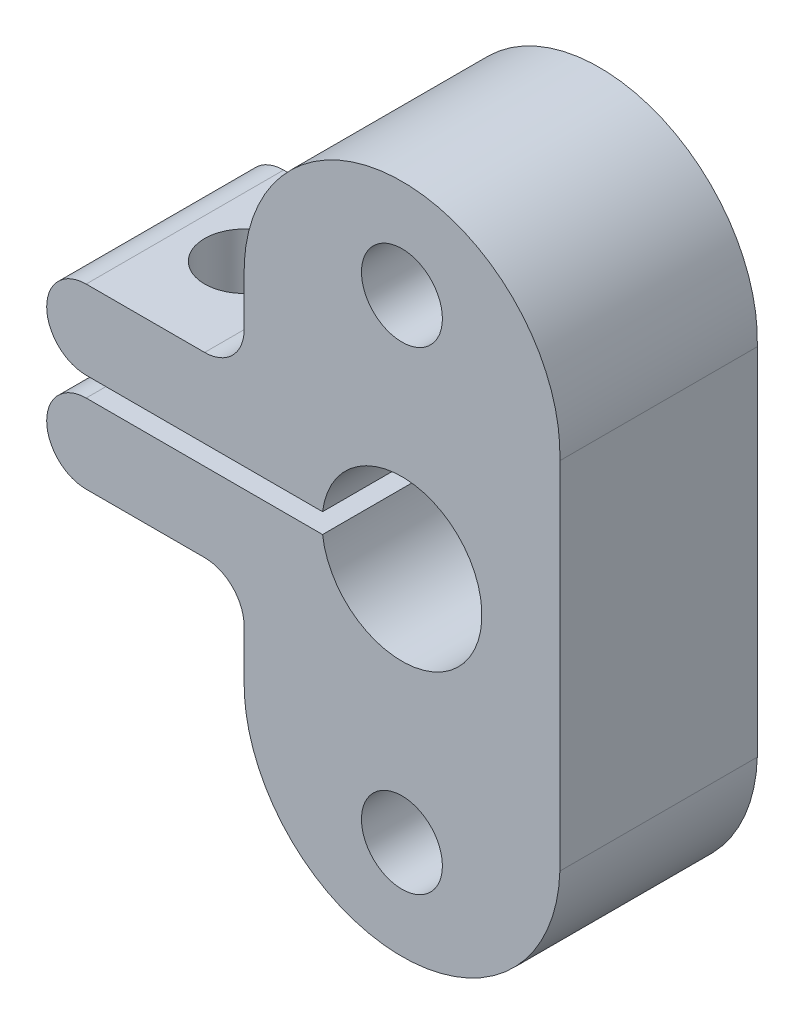
SolidWorks part; units mm, degrees
ref_plane "Plano frontal" through (0, 0, 0) normal (0, 0, 1) x (1, 0, 0)
ref_plane "Plano superior" through (0, 0, 0) normal (0, 1, 0) x (1, 0, 0)
ref_plane "Plano direito" through (0, 0, 0) normal (1, 0, 0) x (0, 0, -1)
sketch "Esboço1" plane through (0, 0, 0) normal (0, 0, 1) x (1, 0, 0)
  line L0 (0.004, -9.0015) -> (0.004, 9.0015) construction
  line L1 (-7.992, -8.75) -> (-7.992, -4.5)
  line L2 (8, -9.253) -> (8, 8.747)
  line L3 (0, 0) -> (-20, 0) construction
  line L4 (-8, -0.5) -> (-17.992, -0.5)
  line L5 (-17.992, -0.5) -> (-17.992, -4.5)
  line L6 (-17.992, -4.5) -> (-7.992, -4.5)
  line L7 (-8, -0.5) -> (-4.019, -0.5)
  line L8 (-8, 0.5) -> (-4.019, 0.5)
  line L9 (-8, 0.5) -> (-17.992, 0.5)
  line L10 (-17.992, 0.5) -> (-17.992, 4.5)
  line L11 (-17.992, 4.5) -> (-7.992, 4.5)
  line L12 (-7.992, 4.5) -> (-7.992, 8.75)
  arc A0 (-4.019, -0.5) -> (-4.019, 0.5) centre (0, 0) ccw
  arc A1 (-7.992, -8.75) -> (8, -9.253) centre (0.004, -9.0015) ccw
  arc A2 (8, 8.747) -> (-7.992, 8.75) centre (0.004, 9.0015) ccw
  circle A3 centre (0, 12) radius 2.05
  circle A4 centre (0, -12) radius 2.05
  point P1 (0.0055, 17.0015)
  point P5 (0, 0)
  point P25 (-0.2475, -16.9976)
  dimension "D1" = 8.1
  dimension "D3" = 8
  dimension "D4" = 4.1
  dimension "D5" = 12
  dimension "D6" = 12
  dimension "D14" = 8
  dimension "D2" = 18
  dimension "D7" = 20
  dimension "D8" = 4
  dimension "D9" = 0.5
  dimension "D10" = 10
  dimension "D11" = 34
  dimension "D12" = 16
  dimension "D13" = 4.25
extrude "Ressalto-extrusão1" add sketch "Esboço1" along normal blind 10
sketch "Esboço2" plane through (0, -4.5, 0) normal (0, -1, 0) x (1, 0, 0)
  line L0 (-17.992, 10) -> (-17.992, 0) construction
  line L1 (-7.992, 0) -> (-17.992, 0) construction
  circle A0 centre (-12.992, 5) radius 2
  dimension "D1" = 4
  dimension "D2" = 5
  dimension "D3" = 5
extrude "Corte-extrusão1" cut sketch "Esboço2" against normal up to surface (9 mm away) up to face at (-12.992, 4.5, 5)
fillet "Filete1" radius 2 6 edges at (-7.992, -4.5, 5) (-7.992, 4.5, 5) (-17.992, -4.5, 5) (-17.992, 0.5, 5) (-17.992, -0.5, 5) (-17.992, 4.5, 5)
